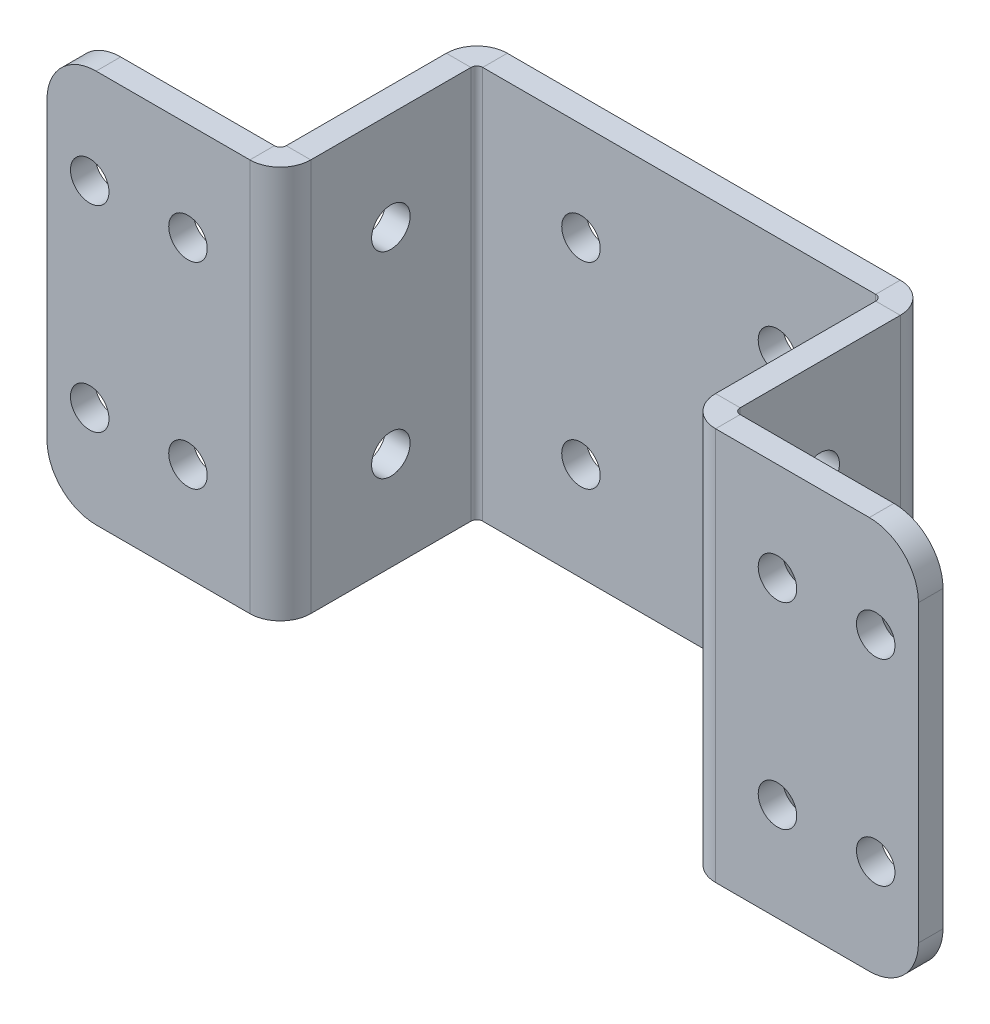
SolidWorks part; units mm, degrees
note: The reader was unsure of these and kept them because the rebuilt part matched: flange length of "Edge-Flange1", "Edge-Flange2".
material "5052-H32"
ref_plane "Front Plane" through (0, 0, 0) normal (0, 0, 1) x (1, 0, 0)
ref_plane "Top Plane" through (0, 0, 0) normal (0, 1, 0) x (1, 0, 0)
ref_plane "Right Plane" through (0, 0, 0) normal (1, 0, 0) x (0, 0, -1)
sketch "Sketch1" plane through (0, 0, 0) normal (0, 0, 1) x (1, 0, 0)
  line L5 (-25.4, 0) -> (25.4, 0)
  line L6 (-25.4, 0) -> (-25.4, 50.8)
  line L7 (-25.4, 50.8) -> (25.4, 50.8)
  line L8 (25.4, 0) -> (25.4, 50.8)
  point P6 (0, 0)
  dimension "D1" = 50.8
  dimension "D2" = 50.8
base flange "Base-Flange1" sketch "Sketch1" thickness 3.175 reverse thickness direction no parameters "D1"=0.762
sketch "Sketch7" plane through (25.4, 0, 0) normal (1, 0, 0) x (0, 0, -1)
  line L1 (3.175, 50.8) -> (-22.225, 50.8)
  line L2 (3.175, 50.8) -> (3.175, 0)
  line L3 (3.175, 0) -> (-22.225, 0)
  line L4 (-22.225, 50.8) -> (-22.225, 0)
  dimension "D1" = 25.4
edge flange "Edge-Flange1" sketch "Sketch12" flange angle 90 flange length 25.4 flange position bend outside bend radius 0.762 thickness 3.175 relief rectangular parameters "D6"=10
sketch "Sketch12" plane through (25.4, 0, 0) normal (1, 0, 0) x (0, 1, 0)
  line L2 (0, 0) -> (0, 22.225)
  line L3 (0, 22.225) -> (50.8, 22.225)
  line L4 (50.8, 22.225) -> (50.8, 0)
  line L11 (0, 0) -> (50.8, 0) construction
  line L12 (0, 0) -> (50.8, 0)
bend "EdgeBend1" bend radius 0.762 bend angle 90 parameters "D5"=1
edge flange "Edge-Flange2" sketch "Sketch15" flange angle 90 flange length 30.1625 flange position material outside bend radius 0.762 thickness 3.175 relief rectangular parameters "D6"=10
sketch "Sketch15" plane through (29.337, 0, 22.225) normal (0, 0, 1) x (0, -1, 0)
  line L2 (-50.8, 0) -> (-50.8, 26.9875)
  line L3 (-50.8, 26.9875) -> (0, 26.9875)
  line L4 (0, 26.9875) -> (0, 0)
  line L11 (-50.8, 0) -> (0, 0) construction
  line L12 (-50.8, 0) -> (0, 0)
  dimension "D1" = 26.9875
bend "EdgeBend2" bend radius 0.762 bend angle 90 parameters "D5"=2
sketch "Sketch16" plane through (29.337, 0, 0) normal (1, 0, 0) x (0, 0, -1)
  line L0 (-0.762, 50.8) -> (-21.463, 50.8) construction
  circle A0 centre (-11.1125, 38.1) radius 2.4892
  circle A1 centre (-11.1125, 12.7) radius 2.4892
  point P5 (-11.1125, 50.8)
  dimension "D1" = 4.9784
  dimension "D2" = 25.4
  dimension "D3" = 12.7
extrude "Cut-Extrude1" cut sketch "Sketch16" against normal up to next normal cut yes
sketch "Sketch17" plane through (0, 0, 22.225) normal (0, 0, -1) x (-1, 0, 0)
  line L0 (-56.3245, 50.8) -> (-30.099, 50.8) construction
  line L2 (-25.4, 0) -> (-25.4, 50.8) construction
  circle A0 centre (-50.8, 38.1) radius 2.4892
  circle A2 centre (-38.1, 38.1) radius 2.4892
  circle A3 centre (-38.1, 12.7) radius 2.4892
  circle A4 centre (-50.8, 12.7) radius 2.4892
  dimension "D3" = 4.9784
  dimension "D4" = 25.4
  dimension "5" = 12.7
  dimension "D5" = 12.7
  dimension "D6" = 12.7
  dimension "D1" = 2
  dimension "D2" = 2
extrude "Cut-Extrude2" cut sketch "Sketch17" against normal up to next normal cut yes
sketch "Sketch18" plane through (0, 0, -3.175) normal (0, 0, -1) x (-1, 0, 0)
  line L0 (-25.4, 50.8) -> (-25.4, 0) construction
  line L1 (-25.4, 50.8) -> (25.4, 50.8) construction
  circle A0 centre (-12.7, 38.1) radius 2.4892
  circle A1 centre (12.7, 38.1) radius 2.4892
  circle A2 centre (12.7, 12.7) radius 2.4892
  circle A3 centre (-12.7, 12.7) radius 2.4892
  dimension "D3" = 4.9784
  dimension "D4" = 12.7
  dimension "D5" = 25.4
  dimension "D6" = 25.4
  dimension "D7" = 12.7
  dimension "D1" = 2
  dimension "D2" = 2
extrude "Cut-Extrude3" cut sketch "Sketch18" against normal up to next normal cut yes
fillet "Fillet1" radius 6.35 2 edges at (56.3245, 0, 23.8125) (56.3245, 50.8, 23.8125)
mirror "Mirror1" about plane through (0, 0, 0) normal (1, 0, 0) of "Fillet1", "Edge-Flange1", "Edge-Flange2", "Cut-Extrude2", "Cut-Extrude1"
bend "MirrorBend1" bend radius 0.762 bend angle 90 parameters "D5"=3
bend "MirrorBend2" bend radius 0.762 bend angle 90 parameters "D5"=4
sketch "Bend-Lines1" [suppressed] plane through (0, 0, 0) normal (0, 1, 0) x (1, 0, 0)
sketch "Bounding-Box1" [suppressed] plane through (0, 0, 0) normal (0, 1, 0) x (1, 0, 0)
sheet metal parameters "Sheet-Metal1" thickness 3.175 parameters "D1"=0.762
flat pattern "Flat-Pattern1" [suppressed]
sketch "Bend-Lines2" plane through (0, 0, 0) normal (0, 1, 0) x (1, 0, 0)
sketch3d "Bounding-Box2" [suppressed]
  line L0 (0, 0, 0) -> (50.8, 0, 0) construction
  line L1 (0, 50.8, 0) -> (50.8, 50.8, 0) construction
  line L2 (0, 0, 0) -> (0, 50.8, 0) construction
  line L3 (50.8, 0, 0) -> (50.8, 50.8, 0) construction
sheet metal parameters "Sheet-Metal3" thickness 3.175 parameters "D1"=0.762
flat pattern "Flat-Pattern1"
sketch "Bend-Lines2" plane through (0, 0, 0) normal (0, 0, 1) x (1, 0, 0)
  line L0 (51.4344, 0) -> (51.4344, 50.8) construction
  line L1 (51.4344, 0) -> (51.4344, 50.8) construction
sketch3d "Bounding-Box2" [suppressed]
  line L0 (0, 0, 0) -> (74.2939, 0, 0) construction
  line L1 (0, 50.8, 0) -> (74.2939, 50.8, 0) construction
  line L2 (0, 0, 0) -> (0, 50.8, 0) construction
  line L3 (74.2939, 0, 0) -> (74.2939, 50.8, 0) construction
bend of the flat pattern "Flatten-<EdgeBend1>1"
sheet metal parameters "Sheet-Metal4" thickness 3.175 parameters "D1"=0.762
flat pattern "Flat-Pattern1"
sketch "Bend-Lines2" plane through (0, 0, 0) normal (0, 0, 1) x (1, 0, 0)
  line L0 (51.4344, 0) -> (51.4344, 50.8) construction
  line L1 (51.4344, 0) -> (51.4344, 50.8) construction
  line L2 (74.9283, 0) -> (74.9283, 50.8) construction
  line L3 (74.9283, 0) -> (74.9283, 50.8) construction
sketch3d "Bounding-Box2" [suppressed]
  line L0 (0, 0, 0) -> (110.4878, 0, 0) construction
  line L1 (0, 50.8, 0) -> (110.4878, 50.8, 0) construction
  line L2 (0, 0, 0) -> (0, 50.8, 0) construction
  line L3 (110.4878, 0, 0) -> (110.4878, 50.8, 0) construction
bend of the flat pattern "Flatten-<EdgeBend1>1"
bend of the flat pattern "Flatten-<EdgeBend2>1"
sheet metal parameters "Sheet-Metal5" thickness 3.175 parameters "D1"=0.762
flat pattern "Flat-Pattern1"
sketch "Bend-Lines2" plane through (0, 0, 0) normal (0, 0, 1) x (1, 0, 0)
  line L0 (51.4344, 0) -> (51.4344, 50.8) construction
  line L1 (51.4344, 0) -> (51.4344, 50.8) construction
  line L2 (74.9283, 0) -> (74.9283, 50.8) construction
  line L3 (74.9283, 0) -> (74.9283, 50.8) construction
sketch3d "Bounding-Box2" [suppressed]
  line L0 (0, 0, 0) -> (110.4878, 0, 0) construction
  line L1 (0, 50.8, 0) -> (110.4878, 50.8, 0) construction
  line L2 (0, 0, 0) -> (0, 50.8, 0) construction
  line L3 (110.4878, 0, 0) -> (110.4878, 50.8, 0) construction
bend of the flat pattern "Flatten-<EdgeBend1>1"
bend of the flat pattern "Flatten-<EdgeBend2>1"
sheet metal parameters "Sheet-Metal6" thickness 3.175 parameters "D1"=0.762
flat pattern "Flat-Pattern1"
sketch "Bend-Lines2" plane through (0, 0, 0) normal (0, 0, 1) x (1, 0, 0)
  line L0 (51.4344, 0) -> (51.4344, 50.8) construction
  line L1 (51.4344, 0) -> (51.4344, 50.8) construction
  line L2 (74.9283, 0) -> (74.9283, 50.8) construction
  line L3 (74.9283, 0) -> (74.9283, 50.8) construction
sketch3d "Bounding-Box2" [suppressed]
  line L0 (0, 0, 0) -> (110.4878, 0, 0) construction
  line L1 (0, 50.8, 0) -> (110.4878, 50.8, 0) construction
  line L2 (0, 0, 0) -> (0, 50.8, 0) construction
  line L3 (110.4878, 0, 0) -> (110.4878, 50.8, 0) construction
bend of the flat pattern "Flatten-<EdgeBend1>1"
bend of the flat pattern "Flatten-<EdgeBend2>1"
sheet metal parameters "Sheet-Metal7" thickness 3.175 parameters "D1"=0.762
flat pattern "Flat-Pattern1"
sketch "Bend-Lines2" plane through (0, 0, 0) normal (0, 0, 1) x (1, 0, 0)
  line L0 (26.0344, 0) -> (26.0344, 50.8) construction
  line L1 (26.0344, 0) -> (26.0344, 50.8) construction
  line L2 (49.5283, 0) -> (49.5283, 50.8) construction
  line L3 (49.5283, 0) -> (49.5283, 50.8) construction
sketch3d "Bounding-Box2" [suppressed]
  line L0 (-25.4, 0, 0) -> (85.0878, 0, 0) construction
  line L1 (-25.4, 50.8, 0) -> (85.0878, 50.8, 0) construction
  line L2 (-25.4, 0, 0) -> (-25.4, 50.8, 0) construction
  line L3 (85.0878, 0, 0) -> (85.0878, 50.8, 0) construction
bend of the flat pattern "Flatten-<EdgeBend1>1"
bend of the flat pattern "Flatten-<EdgeBend2>1"
sheet metal parameters "Sheet-Metal8" thickness 3.175 parameters "D1"=0.762
flat pattern "Flat-Pattern1"
sketch "Bend-Lines2" plane through (0, 0, 0) normal (0, 0, 1) x (1, 0, 0)
  line L0 (26.7964, 0) -> (26.7964, 50.8) construction
  line L1 (26.7964, 0) -> (26.7964, 50.8) construction
  line L2 (50.2903, 0) -> (50.2903, 50.8) construction
  line L3 (50.2903, 0) -> (50.2903, 50.8) construction
  line L4 (-50.2903, 50.8) -> (-50.2903, 0) construction
  line L5 (-26.7964, 50.8) -> (-26.7964, 0) construction
  line L6 (-50.2903, 50.8) -> (-50.2903, 0) construction
  line L7 (-26.7964, 50.8) -> (-26.7964, 0) construction
sketch3d "Bounding-Box2" [suppressed]
  line L0 (-77.9122, 50.8, 0) -> (77.9123, 50.8, 0) construction
  line L1 (-77.9123, 0, 0) -> (77.9122, 0, 0) construction
  line L2 (-77.9122, 50.8, 0) -> (-77.9123, 0, 0) construction
  line L3 (77.9123, 50.8, 0) -> (77.9122, 0, 0) construction
bend of the flat pattern "Flatten-<EdgeBend1>1"
bend of the flat pattern "Flatten-<EdgeBend2>1"
bend of the flat pattern "Flatten-<MirrorBend1>1"
bend of the flat pattern "Flatten-<MirrorBend2>1"
